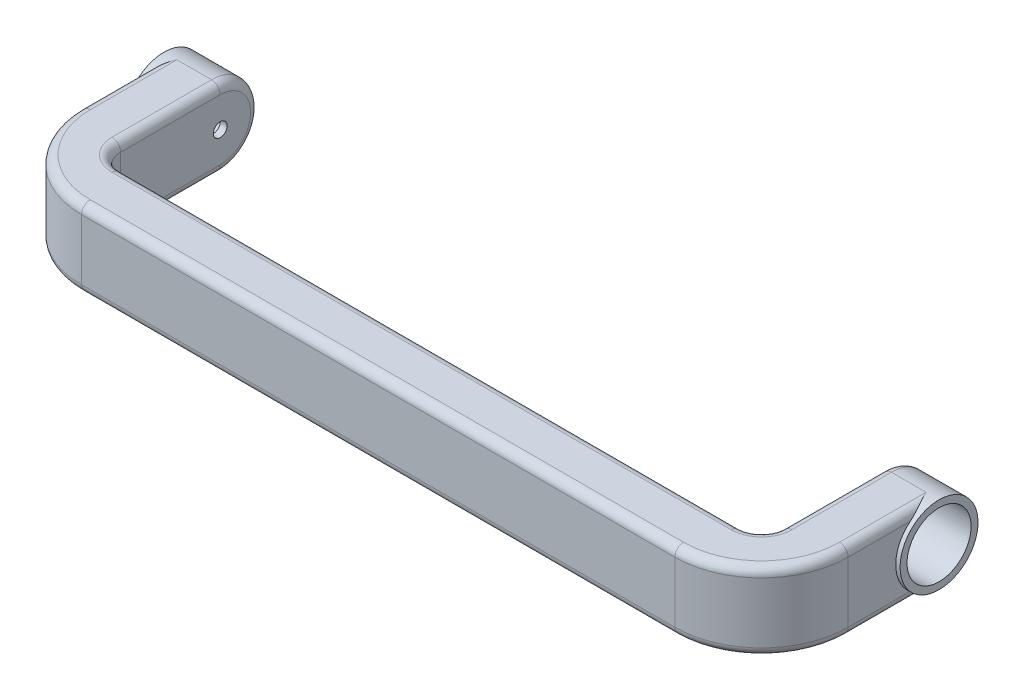
SolidWorks part; units mm, degrees
note: '?' marks a value the reader was unsure of.
ref_plane "Front Plane" through (0, 0, 0) normal (0, 0, 1) x (1, 0, 0)
ref_plane "Top Plane" through (0, 0, 0) normal (0, 1, 0) x (1, 0, 0)
ref_plane "Right Plane" through (0, 0, 0) normal (1, 0, 0) x (0, 0, -1)
sketch "Sketch1" plane through (0, 0, 0) normal (0, 0, 1) x (1, 0, 0)
  line L1 (76.5, -9) -> (-76.5, -9)
  line L2 (76.5, -9) -> (76.5, 9)
  line L3 (76.5, 9) -> (-76.5, 9)
  line L4 (-76.5, -9) -> (-76.5, 9)
  line L5 (76.5, -9) -> (-76.5, 9) construction
  line L6 (76.5, 9) -> (-76.5, -9) construction
  point P0 (0, 0)
  dimension "D1" = 153
  dimension "D2" = 18
extrude "Boss-Extrude1" add sketch "Sketch1" along normal blind 12
sketch "Sketch2" plane through (0, 0, 0) normal (0, 0, -1) x (-1, 0, 0)
  line L0 (76.5, -9) -> (-76.5, -9) construction
  line L1 (76.5, 9) -> (88.5, 9)
  line L2 (76.5, 9) -> (76.5, -9)
  line L3 (76.5, -9) -> (88.5, -9)
  line L4 (88.5, 9) -> (88.5, -9)
  dimension "D1" = 12
extrude "Boss-Extrude2" add sketch "Sketch2" along normal blind 28 and the other way up to surface (12 mm away) other way up to face at (0, 0, 12)
sketch "Sketch3" plane through (-88.5, 0, 0) normal (-1, 0, 0) x (0, 0, 1)
  line L1 (12, 9) -> (-28, 9) construction
  line L2 (12, -9) -> (-28, -9) construction
  line L3 (-28, -9) -> (-28, 9) construction
  circle A0 centre (-28, 0) radius 9
extrude "Boss-Extrude3" add sketch "Sketch3" along normal blind 1 and the other way up to surface
mirror "Mirror1" about plane through (0, 0, 0) normal (1, 0, 0) of "Boss-Extrude2", "Boss-Extrude3"
sketch "Sketch4" plane through (-89.5, 0, 0) normal (-1, 0, 0) x (0, 0, 1)
  arc A2 (-20.6, 0) -> (-20.6, 0) centre (-28, 0) ccw
  circle A3 centre (-28, 0) radius 7.4
  dimension "D1" = 1.6
extrude "Cut-Extrude1" cut sketch "Sketch4" against normal offset from surface (11.4 mm away) 1.6 up to face at (-76.5, 0, -16.25)
sketch "Sketch5" plane through (-78.1, 0, 0) normal (-1, 0, 0) x (0, 0, 1)
  circle A0 centre (-28, 0) radius 1.6
  dimension "D1" = 3.2
extrude "Cut-Extrude2" cut sketch "Sketch5" against normal through all
sketch "Sketch9" plane through (89.5, 0, 0) normal (1, 0, 0) x (0, 0, -1)
  circle A0 centre (28, 0) radius 7.4 construction
  circle A1 centre (28, 0) radius 7.4
extrude "Cut-Extrude4" cut sketch "Sketch9" against normal offset from surface (11.4 mm away) 1.6 up to face at (76.5, 0, -29.6)
ref_axis "Axis1" through (-46.0243, 0, -28) along (-1, 0, 0)?
ref_plane "Plane1" through (0, 0, 0) normal (0, -1, 0) x (-1, 0, 0)
sketch "Sketch6" plane through (0, 0, 0) normal (0, -1, 0) x (-1, 0, 0)
  line L0 (89.5, 35.4) -> (78.1, 29.6)
rib "Rib1" [suppressed] sketch "Sketch6" sketch "Sketch6" thickness 0.8 extrusion direction parallel to sketch draft on yes draft angle 2 parameters "D1"=0.8, "D3"=2
pattern_circular "CirPattern1" [suppressed] count 6 over 360
sketch "Sketch10" plane through (-78.1, 0, 0) normal (-1, 0, 0) x (0, 0, 1)
  circle A0 centre (-28, 0) radius 4
  dimension "D1" = 8
extrude "Boss-Extrude4" [suppressed] add sketch "Sketch10" along normal blind 4
sketch "Sketch7" plane through (-78.1, 0, 0) normal (-1, 0, 0) x (0, 0, 1)
  circle A0 centre (-28, 0) radius 3.5
  dimension "D1" = 7
extrude "Cut-Extrude3" [suppressed] cut sketch "Sketch7" along normal through all
mirror "Mirror2" [suppressed] about plane through (0, 0, 0) normal (1, 0, 0)
fillet "Fillet1" radius 20 2 edges at (88.5, 0, 12) (-88.5, 0, 12)
fillet "Fillet2" radius 5 2 edges at (-76.5, 0, 0) (76.5, 0, 0)
fillet "Fillet3" radius 2 22 edges at (-88.5, -9, -18) (-82.6421, -9, 6.1421) (88.5, 9, -18) (88.5, -9, -18) (82.6421, -9, 6.1421) (75.0355, 9, -1.4645) (76.5, -9, -16.5) (76.5, 9, -16.5) (76.5, 0, -37) (75.0355, -9, -1.4645) (0, -9, 0) (-75.0355, -9, -1.4645) (-76.5, -9, -16.5) (-76.5, 0, -37) (-76.5, 9, -16.5) (-75.0355, 9, -1.4645) (-88.5, 9, -18) (82.6421, 9, 6.1421) (0, 9, 12) (0, -9, 12) (0, 9, 0) (-82.6421, 9, 6.1421)
sketch "Sketch12" plane through (0, -9, 0) normal (0, -1, 0) x (1, 0, 0)
  line L0 (-86.5, -18.4) -> (-256.5, -18.4)
  line L1 (78.5, -18.4) -> (86.5, -18.4)
  line L2 (-46.0243, -28) -> (-80.4774, -28) construction
  line L8 (78.5, -5) -> (78.5, -28)
  line L9 (78.5, -28) -> (86.5, -28)
  line L10 (86.5, -28) -> (86.5, -8)
  line L11 (68.5, 10) -> (-68.5, 10)
  line L12 (-86.5, -8) -> (-86.5, -28)
  line L13 (-86.5, -28) -> (-78.5, -28)
  line L15 (-71.5, 2) -> (71.5, 2)
  line L16 (78.5, -5) -> (78.5, -18.4)
  line L18 (86.5, -18.4) -> (86.5, -8)
  line L19 (68.5, 10) -> (-68.5, 10)
  line L20 (-86.5, -8) -> (-86.5, -18.4)
  line L23 (-71.5, 2) -> (71.5, 2)
  arc A4 (78.5, -5) -> (71.5, 2) centre (71.5, -5) ccw
  arc A5 (86.5, -8) -> (68.5, 10) centre (68.5, -8) ccw
  arc A6 (-68.5, 10) -> (-86.5, -8) centre (-68.5, -8) ccw
  arc A7 (-71.5, 2) -> (-78.5, -5) centre (-71.5, -5) ccw
  arc A8 (78.5, -5) -> (71.5, 2) centre (71.5, -5) ccw
  arc A9 (86.5, -8) -> (68.5, 10) centre (68.5, -8) ccw
  arc A10 (-68.5, 10) -> (-86.5, -8) centre (-68.5, -8) ccw
  arc A11 (-71.5, 2) -> (-78.5, -5) centre (-71.5, -5) ccw
  spline S2 degree 1 poles (-78.5, -3027.9638) (-78.5, 2994.9777) knots -130.433207 -130.433207 131.433814 131.433814 only from (-78.5, -28) to (-78.5, -5)
  spline S3 degree 1 poles (-78.5, -28) (-78.5, -5) knots 0 0 1 1
  dimension "D2" = 9.6
  dimension "D1" = 0
extrude "Cut-Extrude6" [suppressed] cut sketch "Sketch12" against normal offset from surface (16.4 mm away) 1.6
fillet "Fillet4" [suppressed] radius 9
ref_plane "Plane4" [suppressed] through (0, -9, 0) normal (0, -1, 0) x (-1, 0, 0)
sketch "Sketch17" [suppressed] plane through (0, -9, 0) normal (0, -1, 0) x (-1, 0, 0)
  line L0 (-71.5, -2) -> (-71.5, -9.7482)
  arc A0 (-86.5, 8) -> (-68.5, -10) centre (-68.5, 8) ccw construction
rib "Rib5" [suppressed] sketch "Sketch17" sketch "Sketch17" thickness 0.8 extrusion direction normal to sketch draft on no parameters "D1"=0.8
pattern_linear "LPattern1" [suppressed] count 15 spacing 10.2143
sketch "Sketch18" [suppressed] plane through (0, -9, 0) normal (0, -1, 0) x (-1, 0, 0)
  line L0 (-78.5, 16.2) -> (-86.5, 16.2)
  line L1 (-78.5, 5) -> (-78.5, 27.4) construction
  line L2 (-86.5, 8) -> (-86.5, 18.4) construction
rib "Rib6" [suppressed] sketch "Sketch18" sketch "Sketch18" thickness 0.8 extrusion direction normal to sketch draft on no parameters "D1"=0.8
pattern_linear "LPattern2" [suppressed] count 2 spacing 9
sketch "Sketch19" [suppressed] plane through (0, -9, 0) normal (0, -1, 0) x (-1, 0, 0)
  line L0 (-76.4497, 0.0503) -> (-81.2279, -4.7279)
  arc A0 (-78.5, 5) -> (-71.5, -2) centre (-71.5, 5) ccw construction
  arc A1 (-86.5, 8) -> (-68.5, -10) centre (-68.5, 8) ccw construction
rib "Rib7" [suppressed] sketch "Sketch19" sketch "Sketch19" thickness 0.8 extrusion direction normal to sketch draft on no parameters "D1"=0.8
mirror "Mirror3" [suppressed] about plane through (0, 0, 0) normal (1, 0, 0)
